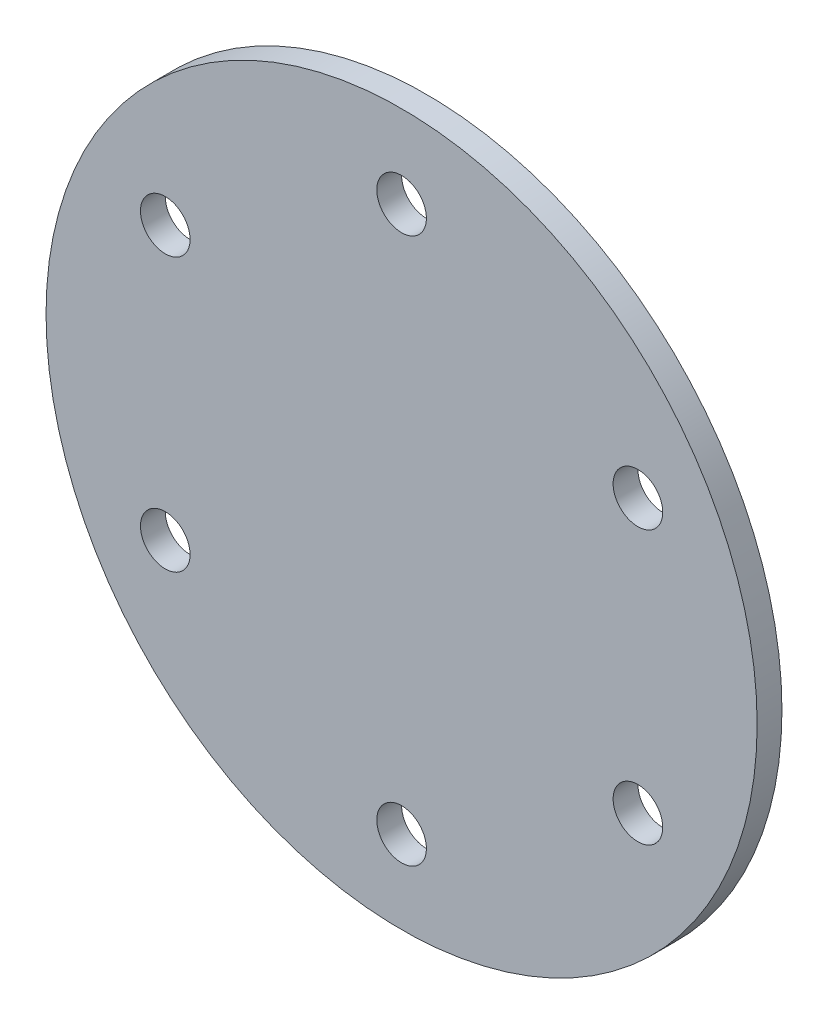
SolidWorks part; units mm, degrees
ref_plane "Front Plane" through (0, 0, 0) normal (0, 0, 1) x (1, 0, 0)
ref_plane "Top Plane" through (0, 0, 0) normal (0, 1, 0) x (1, 0, 0)
ref_plane "Right Plane" through (0, 0, 0) normal (1, 0, 0) x (0, 0, -1)
sketch "Sketch1" plane through (0, 0, 0) normal (0, 0, 1) x (1, 0, 0)
  circle A0 centre (0, 0) radius 43
  circle A1 centre (0, 0) radius 33 construction
  circle A3 centre (0, 33) radius 3
  dimension "D1" = 86
  dimension "D2" = 6
  dimension "D3" = 66
extrude "Boss-Extrude2" add sketch "Sketch1" along normal blind 3 contours A0
extrude "Cut-Extrude1" cut sketch "Sketch1<3>" along normal through all contours A3
sketch "Sketch1<3>" plane through (0, 0, 0) normal (0, 0, 1) x (1, 0, 0) same geometry as "Sketch1"
pattern_circular "CirPattern2" count 6 over 360 about axis through (0, 0, 3) along (0, 0, -1) of "Cut-Extrude1" reverse direction yes
extrude "Cut-Extrude2" cut sketch "Sketch1<4>" along normal through all rebuild error yes
sketch "Sketch1<4>" plane through (0, 0, 0) normal (0, 0, 1) x (1, 0, 0) same geometry as "Sketch1"
